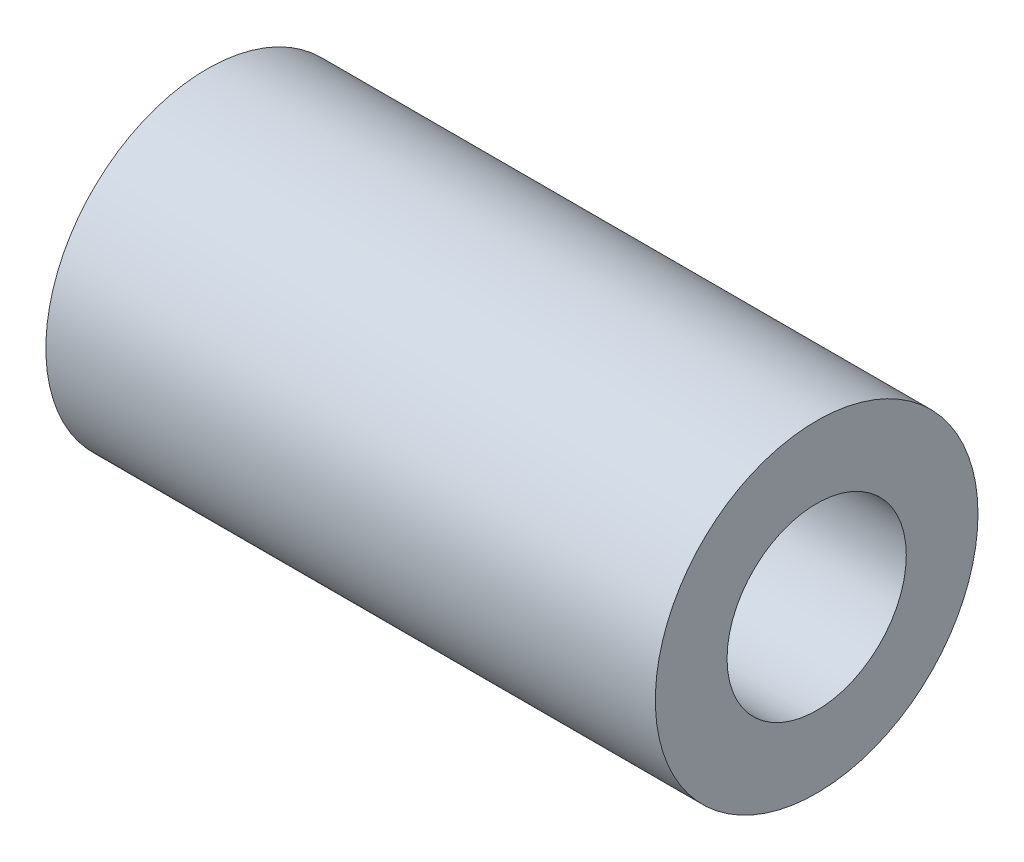
SolidWorks part; units mm, degrees
ref_plane "Front Plane" through (0, 0, 0) normal (0, 0, 1) x (1, 0, 0)
ref_plane "Top Plane" through (0, 0, 0) normal (0, 1, 0) x (1, 0, 0)
ref_plane "Right Plane" through (0, 0, 0) normal (1, 0, 0) x (0, 0, -1)
sketch "Sketch1" plane through (0, 0, 0) normal (1, 0, 0) x (0, 0, -1)
  circle A0 centre (0, 0) radius 2.5
  circle A1 centre (0, 0) radius 4.5
  dimension "D1" = 2
extrude "Boss-Extrude1" add sketch "Sketch1" along normal blind 17
